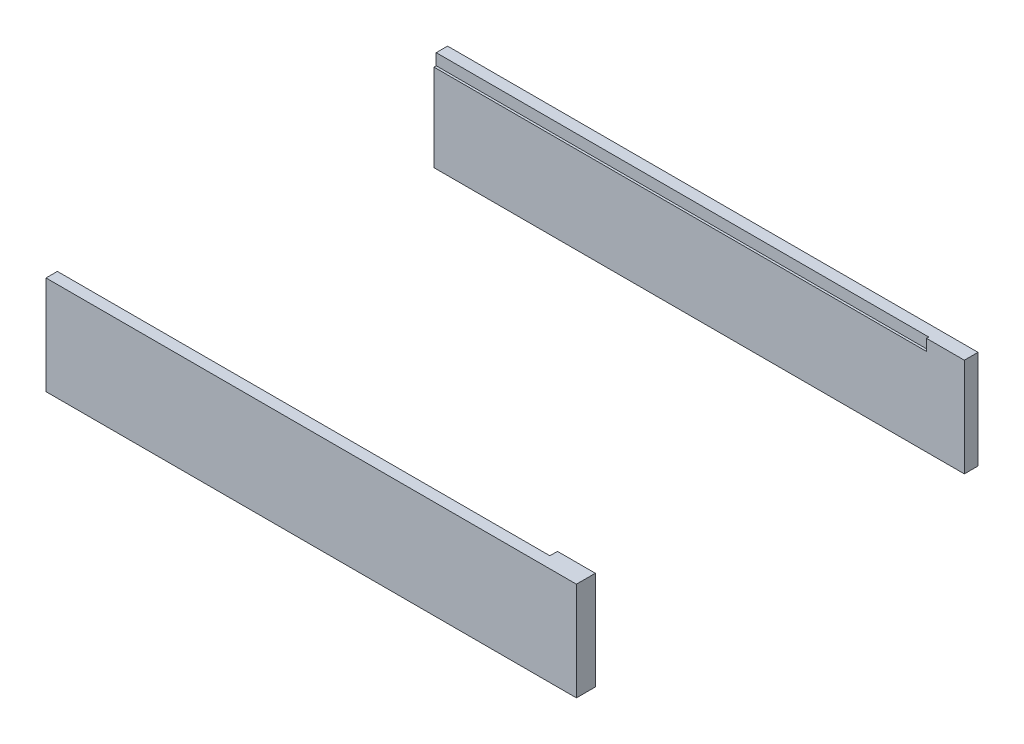
SolidWorks part; units mm, degrees
ref_plane "Front Plane" through (0, 0, 0) normal (0, 0, 1) x (1, 0, 0)
ref_plane "Top Plane" through (0, 0, 0) normal (0, 1, 0) x (1, 0, 0)
ref_plane "Right Plane" through (0, 0, 0) normal (1, 0, 0) x (0, 0, -1)
sketch "Sketch3" plane through (0, 0, 0) normal (0, 1, 0) x (1, 0, 0)
  line L1 (-39.8113, 2.7358) -> (30.1887, 2.7358)
  line L2 (-39.8113, 2.7358) -> (-39.8113, 0.9358)
  line L3 (-39.8113, 0.9358) -> (30.1887, 0.9358)
  line L4 (30.1887, 2.7358) -> (30.1887, 0.9358)
  line L5 (-39.8113, -50.2642) -> (30.1887, -50.2642)
  line L6 (-39.8113, -50.2642) -> (-39.8113, -47.7642)
  line L7 (-39.8113, -47.7642) -> (30.1887, -47.7642)
  line L8 (30.1887, -50.2642) -> (30.1887, -47.7642)
  point P10 (-39.8113, -49.0142)
  dimension "D1" = 70
  dimension "D2" = 1.8
  dimension "D3" = 2.5
  dimension "D4" = 53
  dimension "D5" = 0
extrude "Boss-Extrude1" add sketch "Sketch3" along normal blind 13
sketch "Sketch4" plane through (0, 13, 0) normal (0, 1, 0) x (1, 0, 0)
  line L1 (-39.8113, -47.7642) -> (25.1887, -47.7642)
  line L2 (-39.8113, -47.7642) -> (-39.8113, -48.7642)
  line L3 (-39.8113, -48.7642) -> (25.1887, -48.7642)
  line L4 (25.1887, -47.7642) -> (25.1887, -48.7642)
  dimension "D1" = 1
  dimension "D2" = 65
extrude "Cut-Extrude1" cut sketch "Sketch4" against normal blind 1.5
sketch "Sketch5" plane through (0, 13, 0) normal (0, 1, 0) x (1, 0, 0)
  line L1 (-39.8113, 0.9358) -> (25.1887, 0.9358)
  line L2 (-39.8113, 0.9358) -> (-39.8113, 1.2358)
  line L3 (-39.8113, 1.2358) -> (25.1887, 1.2358)
  line L4 (25.1887, 0.9358) -> (25.1887, 1.2358)
  dimension "D1" = 65
  dimension "D2" = 0.3
extrude "Cut-Extrude2" cut sketch "Sketch5" against normal blind 1.5
sketch "Sketch6" plane through (0, 0, 50.2642) normal (0, 0, 1) x (1, 0, 0)
  line L0 (-39.8113, 0) -> (30.1887, 0) construction
  line L1 (-39.8113, 13) -> (-39.8113, 0) construction
  circle A0 centre (-19.8113, 6.5) radius 5.35
  dimension "D1" = 10.7
  dimension "D2" = 6.5
  dimension "D3" = 20
